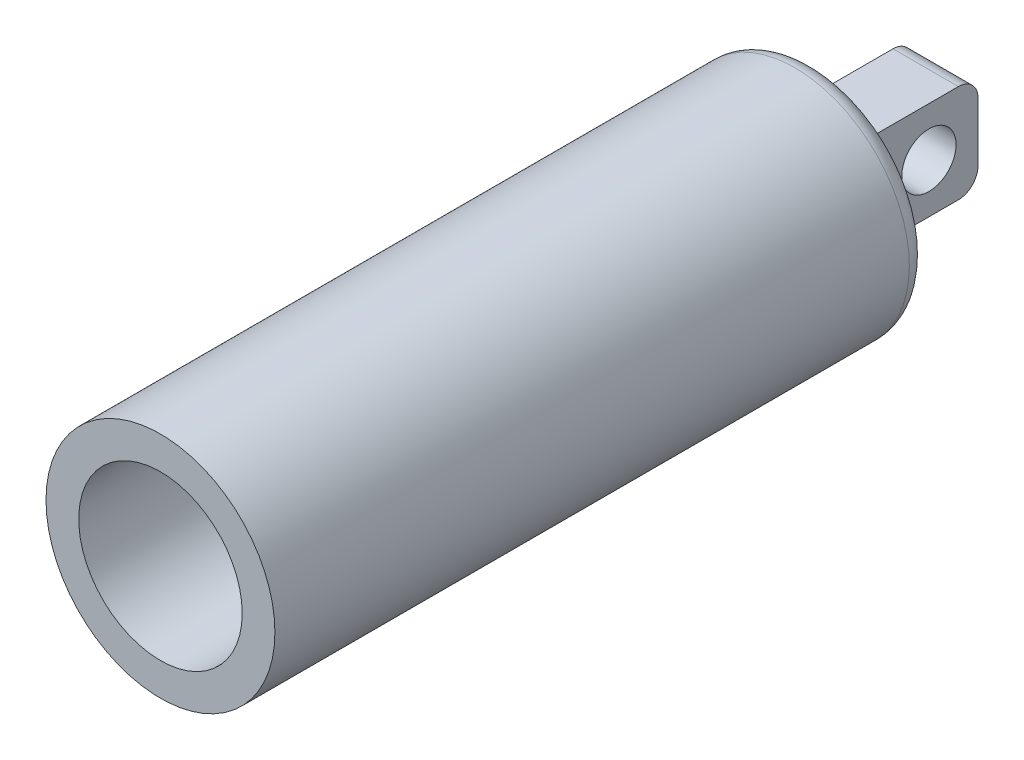
SolidWorks part; units mm, degrees
ref_plane "Front Plane" through (0, 0, 0) normal (0, 0, 1) x (1, 0, 0)
ref_plane "Top Plane" through (0, 0, 0) normal (0, 1, 0) x (1, 0, 0)
ref_plane "Right Plane" through (0, 0, 0) normal (1, 0, 0) x (0, 0, -1)
sketch "Sketch1" plane through (0, 0, 0) normal (0, 0, 1) x (1, 0, 0)
  circle A0 centre (0, 0) radius 17.5
  dimension "D1" = 35
extrude "Boss-Extrude1" add sketch "Sketch1" along normal blind 100
sketch "Sketch2" plane through (0, 0, 100) normal (0, 0, 1) x (1, 0, 0)
  circle A0 centre (0, 0) radius 12.5
  dimension "D1" = 25
extrude "Cut-Extrude1" cut sketch "Sketch2" against normal blind 90
sketch "Sketch3" plane through (0, 0, 0) normal (1, 0, 0) x (0, 0, -1)
  line L0 (0, 0) -> (20, 0) construction
  line L1 (0, 7.5) -> (0, -7.5)
  line L2 (0, -17.5) -> (0, 17.5) construction
  line L3 (0, -7.5) -> (20, -7.5)
  line L4 (20, -7.5) -> (20, 7.5)
  line L5 (20, 7.5) -> (0, 7.5)
  circle A0 centre (12.5, 0) radius 4.15
  point P10 (20, 0)
  dimension "D3" = 8.3
  dimension "D4" = 7.5
  dimension "D1" = 15
  dimension "D2" = 20
extrude "Boss-Extrude2" add sketch "Sketch3" along normal blind 5 and the other way blind 5
fillet "Fillet1" radius 3 7 edges at (0, -7.5, 0) (17.5, 0, 0) (0, -7.5, -20) (-5, 0, 0) (0, 7.5, -20) (5, 0, 0) (0, 7.5, 0)
